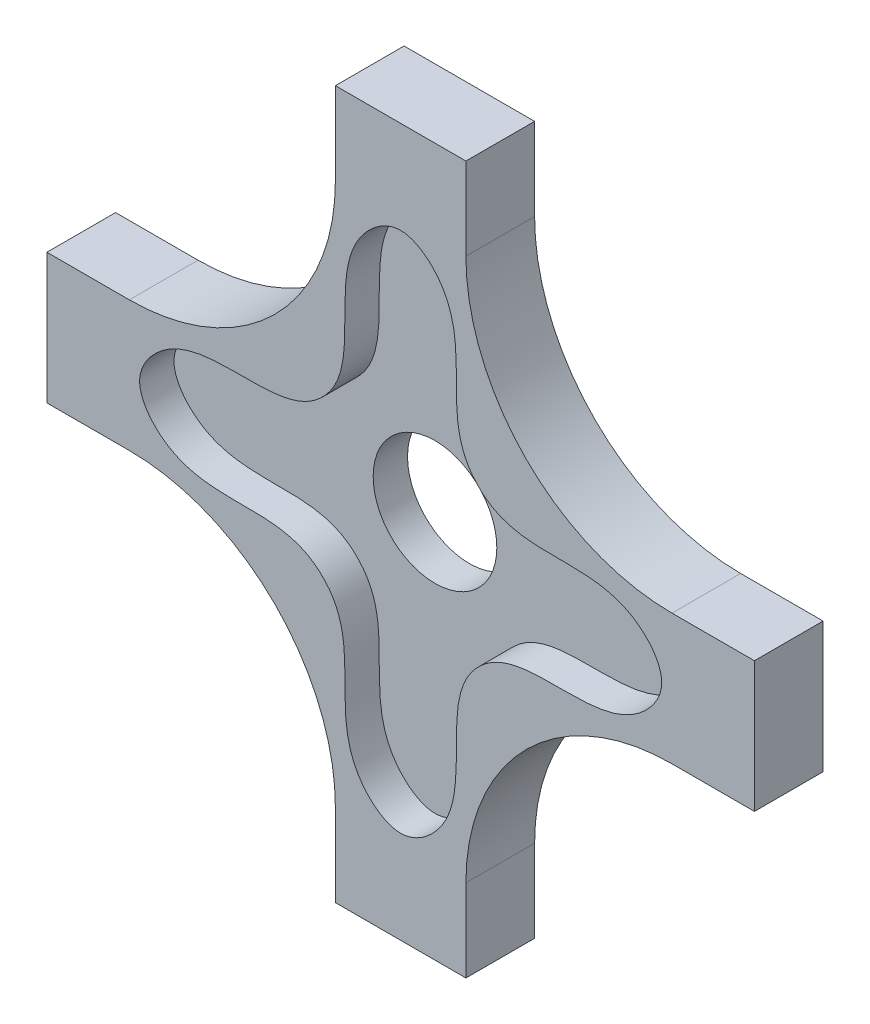
SolidWorks part; units mm, degrees
ref_plane "Front Plane" through (0, 0, 0) normal (0, 0, 1) x (1, 0, 0)
ref_plane "Top Plane" through (0, 0, 0) normal (0, 1, 0) x (1, 0, 0)
ref_plane "Right Plane" through (0, 0, 0) normal (1, 0, 0) x (0, 0, -1)
sketch "Sketch1" plane through (0, 0, 0) normal (0, 0, 1) x (1, 0, 0)
  line L0 (-4.75, -19.75) -> (-4.75, -25.75)
  line L1 (-4.75, 25.75) -> (4.75, 25.75)
  line L2 (-4.75, 25.75) -> (-4.75, 19.75)
  line L3 (-4.75, -25.75) -> (4.75, -25.75)
  line L4 (4.75, 25.75) -> (4.75, 19.75)
  line L5 (-4.75, 25.75) -> (4.75, -25.75) construction
  line L6 (-4.75, -25.75) -> (4.75, 25.75) construction
  line L7 (-25.75, 4.75) -> (-19.75, 4.75)
  line L8 (-25.75, 4.75) -> (-25.75, -4.75)
  line L9 (-25.75, -4.75) -> (-19.75, -4.75)
  line L10 (25.75, 4.75) -> (25.75, -4.75)
  line L11 (-25.75, 4.75) -> (25.75, -4.75) construction
  line L12 (-25.75, -4.75) -> (25.75, 4.75) construction
  line L13 (4.75, -19.75) -> (4.75, -25.75)
  line L14 (19.75, -4.75) -> (25.75, -4.75)
  line L15 (19.75, 4.75) -> (25.75, 4.75)
  arc A0 (-19.75, -4.75) -> (-4.75, -19.75) centre (-19.75, -19.75) cw
  arc A1 (4.75, -19.75) -> (19.75, -4.75) centre (19.75, -19.75) cw
  arc A2 (19.75, 4.75) -> (4.75, 19.75) centre (19.75, 19.75) cw
  arc A3 (-4.75, 19.75) -> (-19.75, 4.75) centre (-19.75, 19.75) cw
  point P0 (0, 0)
  point P6 (0, 0)
  point P19 (4.75, -4.75)
  point P22 (4.75, 4.75)
  dimension "D5" = 15
  dimension "D1" = 51.5
  dimension "D2" = 51.5
  dimension "D3" = 9.5
  dimension "D4" = 9.5
extrude "Boss-Extrude1" add sketch "Sketch1" along normal blind 5
sketch "Sketch2" plane through (0, 0, 5) normal (0, 0, 1) x (1, 0, 0)
  line L0 (0, 0) -> (0, 19) construction
  line L1 (-3, 17) -> (3, 17) construction
  line L2 (-5, 6.5) -> (5, 6.5) construction
  line L3 (17, 3) -> (17, -3) construction
  line L4 (6.5, 5) -> (6.5, -5) construction
  line L5 (0, 0) -> (19, 0) construction
  line L6 (3, -17) -> (-3, -17) construction
  line L7 (5, -6.5) -> (-5, -6.5) construction
  line L8 (0, 0) -> (0, -19) construction
  line L9 (-17, -3) -> (-17, 3) construction
  line L10 (-6.5, -5) -> (-6.5, 5) construction
  line L11 (0, 0) -> (-19, 0) construction
  circle A0 centre (0, 0) radius 19 construction
  spline S0 degree 3 poles (-5.7232, 15.3067) (0, 19.9316) (5.7232, 15.3067) (2.6964, 8.5952) (8.5952, 2.6964) (15.3067, 5.7232) (19.9316, 0) (15.3067, -5.7232) (8.5952, -2.6964) (2.6964, -8.5952) (5.7232, -15.3067) (0, -19.9316) (-5.7232, -15.3067) (-2.6964, -8.5952) (-8.5952, -2.6964) (-15.3067, -5.7232) (-19.9316, 0) (-15.3067, 5.7232) (-8.5952, 2.6964) (-2.6964, 8.5952) (-5.7232, 15.3067) (0, 19.9316) (5.7232, 15.3067) knots -0.133634 -0.116366 -0.029352 0 0.029352 0.116366 0.133634 0.220648 0.25 0.279352 0.366366 0.383634 0.470648 0.5 0.529352 0.616366 0.633634 0.720648 0.75 0.779352 0.866366 0.883634 0.970648 1 1.029352 1.116366 1.133634 only from (0, 19) to (0, 19)
  point P9 (0, 6.5)
  point P10 (0, 17)
  point P18 (6.5, 0)
  point P19 (17, 0)
  point P25 (0, -6.5)
  point P26 (0, -17)
  point P32 (-6.5, 0)
  point P33 (-17, 0)
  point P34 (0, 0)
  dimension "D1" = 38
  dimension "D2" = 3
  dimension "D3" = 5
  dimension "D4" = 6.5
  dimension "D5" = 17
  dimension "D6" = 4
extrude "Cut-Extrude1" cut sketch "Sketch2" against normal blind 2.5
sketch "Sketch3" plane through (0, 0, 0) normal (0, 0, -1) x (-1, 0, 0)
  line L0 (-25.75, 0) -> (25.75, 0) construction
  line L1 (-25.75, -4.75) -> (-25.75, 4.75) construction
  line L2 (25.75, 4.75) -> (25.75, -4.75) construction
  line L3 (0, -25.75) -> (0, 25.75) construction
  line L4 (4.75, -25.75) -> (-4.75, -25.75) construction
  line L5 (-4.75, 25.75) -> (4.75, 25.75) construction
  circle A0 centre (0, 0) radius 4.5
  dimension "D1" = 9
extrude "Cut-Extrude2" cut sketch "Sketch3" against normal through all
